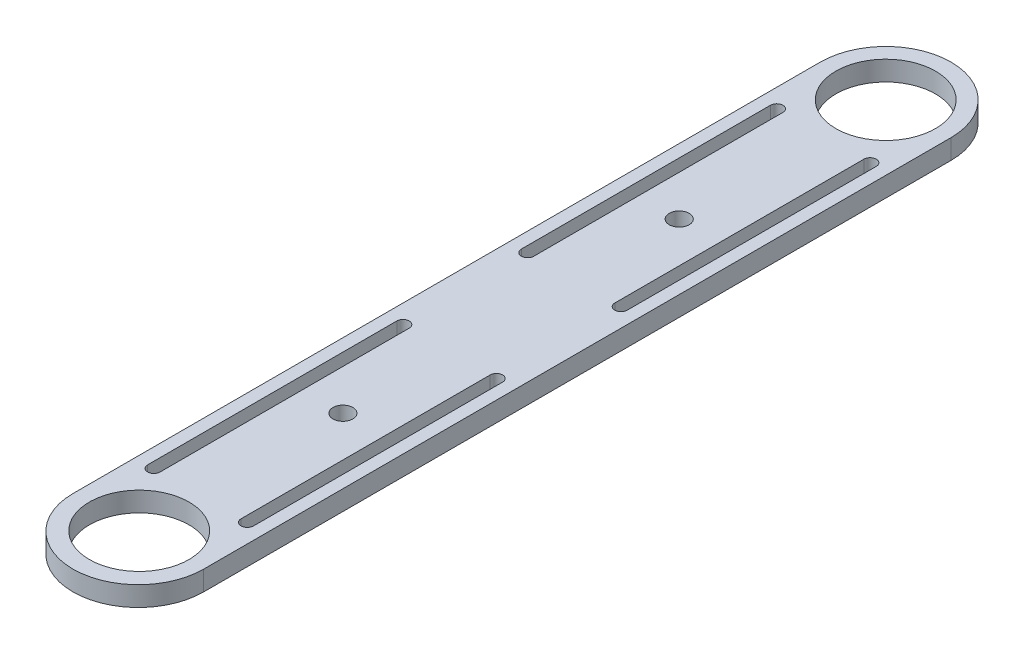
SolidWorks part; units mm, degrees
ref_plane "Front Plane" through (0, 0, 0) normal (0, 0, 1) x (1, 0, 0)
ref_plane "Top Plane" through (0, 0, 0) normal (0, 1, 0) x (1, 0, 0)
ref_plane "Right Plane" through (0, 0, 0) normal (1, 0, 0) x (0, 0, -1)
sketch "Sketch1" plane through (0, 0, 0) normal (0, 1, 0) x (1, 0, 0)
  line L0 (-10.5, 0) -> (-10.5, -120)
  line L1 (10.5, 0) -> (10.5, -120)
  arc A0 (10.5, 0) -> (-10.5, 0) centre (0, 0) ccw
  arc A1 (-10.5, -120) -> (10.5, -120) centre (0, -120) ccw
  dimension "D1" = 10.5
  dimension "D2" = 120
extrude "Boss-Extrude1" add sketch "Sketch1" along normal blind 3.175
sketch "Sketch3" plane through (0, 0, 0) normal (0, -1, 0) x (1, 0, 0)
  line L0 (-8.5, 110) -> (-8.5, 70) construction
  line L1 (-6.5, 70) -> (-6.5, 110) construction
  line L2 (6.5, 110) -> (6.5, 70) construction
  line L3 (8.5, 70) -> (8.5, 110) construction
  line L4 (8.5, 10) -> (8.5, 50) construction
  line L5 (6.5, 50) -> (6.5, 10) construction
  line L6 (-8.5, 50) -> (-8.5, 10) construction
  line L7 (-6.5, 10) -> (-6.5, 50) construction
  line L8 (-8.5, 110) -> (-8.5, 70)
  line L9 (-6.5, 70) -> (-6.5, 110)
  line L10 (6.5, 110) -> (6.5, 70)
  line L11 (8.5, 70) -> (8.5, 110)
  line L12 (8.5, 10) -> (8.5, 50)
  line L13 (6.5, 50) -> (6.5, 10)
  line L14 (-8.5, 50) -> (-8.5, 10)
  line L15 (-6.5, 10) -> (-6.5, 50)
  arc A1 (-8.5, 70) -> (-6.5, 70) centre (-7.5, 70) ccw construction
  arc A2 (8.5, 110) -> (6.5, 110) centre (7.5, 110) ccw construction
  arc A3 (6.5, 70) -> (8.5, 70) centre (7.5, 70) ccw construction
  arc A4 (6.5, 10) -> (8.5, 10) centre (7.5, 10) ccw construction
  arc A5 (8.5, 50) -> (6.5, 50) centre (7.5, 50) ccw construction
  arc A6 (-6.5, 50) -> (-8.5, 50) centre (-7.5, 50) ccw construction
  arc A7 (-8.5, 10) -> (-6.5, 10) centre (-7.5, 10) ccw construction
  arc A8 (-8.5, 70) -> (-6.5, 70) centre (-7.5, 70) ccw
  arc A9 (8.5, 110) -> (6.5, 110) centre (7.5, 110) ccw
  arc A10 (6.5, 70) -> (8.5, 70) centre (7.5, 70) ccw
  arc A11 (6.5, 10) -> (8.5, 10) centre (7.5, 10) ccw
  arc A12 (8.5, 50) -> (6.5, 50) centre (7.5, 50) ccw
  arc A13 (-6.5, 50) -> (-8.5, 50) centre (-7.5, 50) ccw
  arc A14 (-8.5, 10) -> (-6.5, 10) centre (-7.5, 10) ccw
  arc A15 (-6.5, 110) -> (-8.5, 110) centre (-7.5, 110) ccw construction
  arc A16 (-6.5, 110) -> (-8.5, 110) centre (-7.5, 110) ccw
extrude "Cut-Extrude2" cut sketch "Sketch3" against normal through all both and the other way through all
sketch "Sketch4" plane through (0, 3.175, 0) normal (0, 1, 0) x (1, 0, 0)
  circle A0 centre (0, -33.15) radius 1.6 construction
  circle A1 centre (0, -87.15) radius 1.6 construction
  circle A2 centre (0, -33.15) radius 1.6
  circle A3 centre (0, -87.15) radius 1.6
extrude "Cut-Extrude3" cut sketch "Sketch4" against normal through all both and the other way through all
sketch "Sketch5" plane through (0, 3.175, 0) normal (0, 1, 0) x (1, 0, 0)
  circle A0 centre (0, 0) radius 8 construction
  circle A1 centre (-0.008, -119.8502) radius 8 construction
  circle A2 centre (0, 0) radius 8
  circle A3 centre (-0.008, -119.8502) radius 8
extrude "Cut-Extrude4" cut sketch "Sketch5" against normal through all both and the other way through all
